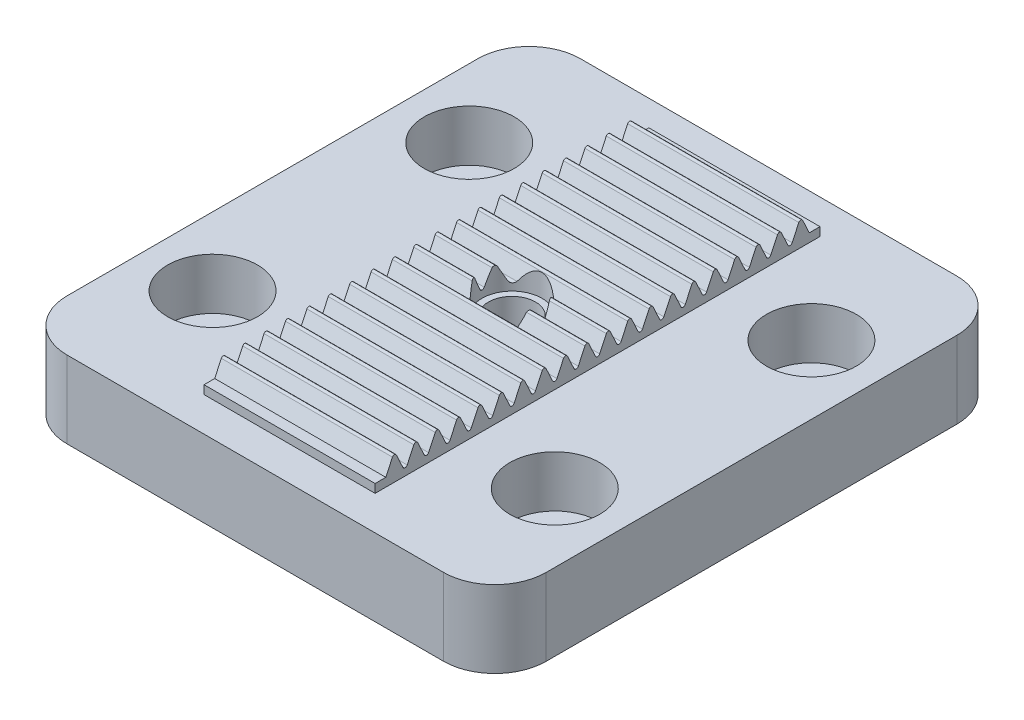
SolidWorks part; units mm, degrees
ref_plane "Front Plane" through (0, 0, 0) normal (0, 0, 1) x (1, 0, 0)
ref_plane "Top Plane" through (0, 0, 0) normal (0, 1, 0) x (1, 0, 0)
ref_plane "Right Plane" through (0, 0, 0) normal (1, 0, 0) x (0, 0, -1)
sketch "Sketch1" plane through (0, 0, 0) normal (0, 1, 0) x (1, 0, 0)
  line L1 (-28, -30) -> (28, -30)
  line L2 (-28, -30) -> (-28, 30)
  line L3 (-28, 30) -> (28, 30)
  line L4 (28, -30) -> (28, 30)
  line L5 (-28, -30) -> (28, 30) construction
  line L6 (-28, 30) -> (28, -30) construction
  line L7 (-20, -15) -> (20, -15) construction
  line L8 (-20, -15) -> (-20, 15) construction
  line L9 (-20, 15) -> (20, 15) construction
  line L10 (20, -15) -> (20, 15) construction
  line L11 (-20, -15) -> (20, 15) construction
  line L12 (-20, 15) -> (20, -15) construction
  circle A0 centre (-20, 15) radius 3.25
  circle A1 centre (-20, -15) radius 3.25
  circle A2 centre (20, -15) radius 3.25
  circle A3 centre (20, 15) radius 3 construction
  circle A4 centre (20, 15) radius 3.25
  point P0 (0, 0)
  point P6 (0, 0)
  point P17 (0, 0)
  point P18 (0, 0)
  dimension "D4" = 6
  dimension "D1" = 60
  dimension "D2" = 56
  dimension "D5" = 40
  dimension "D6" = 30
  dimension "D3" = 0.25
extrude "Boss-Extrude1" add sketch "Sketch1" along normal blind 3
sketch "Sketch2" plane through (0, 3, 0) normal (0, 1, 0) x (1, 0, 0)
  line L4 (28, -30) -> (28, 30)
  line L5 (28, 30) -> (-28, 30)
  line L6 (-28, 30) -> (-28, -30)
  line L7 (-28, -30) -> (28, -30)
  line L8 (28, -30) -> (28, 30)
  line L9 (28, 30) -> (-28, 30)
  line L10 (-28, 30) -> (-28, -30)
  line L11 (-28, -30) -> (28, -30)
  circle A0 centre (-20, 15) radius 5.25
  circle A1 centre (-20, -15) radius 5.25
  circle A2 centre (20, -15) radius 5.25
  circle A3 centre (20, 15) radius 5 construction
  circle A4 centre (20, 15) radius 5.25
  point P14 (0, 0)
  point P16 (18.0466, 14.3998)
  dimension "D3" = 10
  dimension "D2" = 0.25
extrude "Boss-Extrude2" add sketch "Sketch2" along normal blind 6
fillet "Fillet1" radius 6 4 edges at (28, 4.5, -30) (-28, 4.5, -30) (-28, 4.5, 30) (28, 4.5, 30)
sketch "Sketch3" plane through (0, 0, 0) normal (1, 0, 0) x (0, 0, -1)
  line L0 (-26, 9) -> (-26, 10)
  line L1 (-26, 10) -> (-24.75, 10)
  line L3 (24.75, 10) -> (26, 10)
  line L4 (26, 10) -> (26, 9)
  line L5 (26, 9) -> (-26, 9)
  line L6 (-26, 9) -> (-30, 9) construction
  line L7 (26, 9) -> (30, 9) construction
  line L8 (-24.75, 10) -> (-23.9766, 11.6586)
  line L9 (-23.5234, 11.6586) -> (-22.75, 10)
  line L10 (-23.75, 12.1445) -> (-23.75, 10) construction
  line L13 (-24.75, 10) -> (-22.75, 10) construction
  line L14 (-22.75, 10) -> (-22.25, 10) construction
  line L15 (-22.25, 10) -> (-21.4766, 11.6586)
  line L16 (-21.0234, 11.6586) -> (-20.25, 10)
  line L17 (-19.75, 10) -> (-18.9766, 11.6586)
  line L18 (-18.5234, 11.6586) -> (-17.75, 10)
  line L19 (-17.25, 10) -> (-16.4766, 11.6586)
  line L20 (-16.0234, 11.6586) -> (-15.25, 10)
  line L21 (-14.75, 10) -> (-13.9766, 11.6586)
  line L22 (-13.5234, 11.6586) -> (-12.75, 10)
  line L23 (-12.25, 10) -> (-11.4766, 11.6586)
  line L24 (-11.0234, 11.6586) -> (-10.25, 10)
  line L25 (-9.75, 10) -> (-8.9766, 11.6586)
  line L26 (-8.5234, 11.6586) -> (-7.75, 10)
  line L27 (-7.25, 10) -> (-6.4766, 11.6586)
  line L28 (-6.0234, 11.6586) -> (-5.25, 10)
  line L29 (-4.75, 10) -> (-3.9766, 11.6586)
  line L30 (-3.5234, 11.6586) -> (-2.75, 10)
  line L31 (-2.25, 10) -> (-1.4766, 11.6586)
  line L32 (-1.0234, 11.6586) -> (-0.25, 10)
  line L33 (0.25, 10) -> (1.0234, 11.6586)
  line L34 (1.4766, 11.6586) -> (2.25, 10)
  line L35 (2.75, 10) -> (3.5234, 11.6586)
  line L36 (3.9766, 11.6586) -> (4.75, 10)
  line L37 (5.25, 10) -> (6.0234, 11.6586)
  line L38 (6.4766, 11.6586) -> (7.25, 10)
  line L39 (7.75, 10) -> (8.5234, 11.6586)
  line L40 (8.9766, 11.6586) -> (9.75, 10)
  line L41 (10.25, 10) -> (11.0234, 11.6586)
  line L42 (11.4766, 11.6586) -> (12.25, 10)
  line L43 (12.75, 10) -> (13.5234, 11.6586)
  line L44 (13.9766, 11.6586) -> (14.75, 10)
  line L45 (15.25, 10) -> (16.0234, 11.6586)
  line L46 (16.4766, 11.6586) -> (17.25, 10)
  line L47 (17.75, 10) -> (18.5234, 11.6586)
  line L48 (18.9766, 11.6586) -> (19.75, 10)
  line L49 (20.25, 10) -> (21.0234, 11.6586)
  line L50 (21.4766, 11.6586) -> (22.25, 10)
  line L51 (22.75, 10) -> (23.5234, 11.6586)
  line L52 (23.9766, 11.6586) -> (24.75, 10)
  arc A0 (-23.9766, 11.6586) -> (-23.5234, 11.6586) centre (-23.75, 11.553) cw
  arc A1 (-22.75, 10) -> (-22.25, 10) centre (-22.5, 10.1166) ccw
  arc A2 (-21.4766, 11.6586) -> (-21.0234, 11.6586) centre (-21.25, 11.553) cw
  arc A3 (-20.25, 10) -> (-19.75, 10) centre (-20, 10.1166) ccw
  arc A4 (-18.9766, 11.6586) -> (-18.5234, 11.6586) centre (-18.75, 11.553) cw
  arc A5 (-17.75, 10) -> (-17.25, 10) centre (-17.5, 10.1166) ccw
  arc A6 (-16.4766, 11.6586) -> (-16.0234, 11.6586) centre (-16.25, 11.553) cw
  arc A7 (-15.25, 10) -> (-14.75, 10) centre (-15, 10.1166) ccw
  arc A8 (-13.9766, 11.6586) -> (-13.5234, 11.6586) centre (-13.75, 11.553) cw
  arc A9 (-12.75, 10) -> (-12.25, 10) centre (-12.5, 10.1166) ccw
  arc A10 (-11.4766, 11.6586) -> (-11.0234, 11.6586) centre (-11.25, 11.553) cw
  arc A11 (-10.25, 10) -> (-9.75, 10) centre (-10, 10.1166) ccw
  arc A12 (-8.9766, 11.6586) -> (-8.5234, 11.6586) centre (-8.75, 11.553) cw
  arc A13 (-7.75, 10) -> (-7.25, 10) centre (-7.5, 10.1166) ccw
  arc A14 (-6.4766, 11.6586) -> (-6.0234, 11.6586) centre (-6.25, 11.553) cw
  arc A15 (-5.25, 10) -> (-4.75, 10) centre (-5, 10.1166) ccw
  arc A16 (-3.9766, 11.6586) -> (-3.5234, 11.6586) centre (-3.75, 11.553) cw
  arc A17 (-2.75, 10) -> (-2.25, 10) centre (-2.5, 10.1166) ccw
  arc A18 (-1.4766, 11.6586) -> (-1.0234, 11.6586) centre (-1.25, 11.553) cw
  arc A19 (-0.25, 10) -> (0.25, 10) centre (0, 10.1166) ccw
  arc A20 (1.0234, 11.6586) -> (1.4766, 11.6586) centre (1.25, 11.553) cw
  arc A21 (2.25, 10) -> (2.75, 10) centre (2.5, 10.1166) ccw
  arc A22 (3.5234, 11.6586) -> (3.9766, 11.6586) centre (3.75, 11.553) cw
  arc A23 (4.75, 10) -> (5.25, 10) centre (5, 10.1166) ccw
  arc A24 (6.0234, 11.6586) -> (6.4766, 11.6586) centre (6.25, 11.553) cw
  arc A25 (7.25, 10) -> (7.75, 10) centre (7.5, 10.1166) ccw
  arc A26 (8.5234, 11.6586) -> (8.9766, 11.6586) centre (8.75, 11.553) cw
  arc A27 (9.75, 10) -> (10.25, 10) centre (10, 10.1166) ccw
  arc A28 (11.0234, 11.6586) -> (11.4766, 11.6586) centre (11.25, 11.553) cw
  arc A29 (12.25, 10) -> (12.75, 10) centre (12.5, 10.1166) ccw
  arc A30 (13.5234, 11.6586) -> (13.9766, 11.6586) centre (13.75, 11.553) cw
  arc A31 (14.75, 10) -> (15.25, 10) centre (15, 10.1166) ccw
  arc A32 (16.0234, 11.6586) -> (16.4766, 11.6586) centre (16.25, 11.553) cw
  arc A33 (17.25, 10) -> (17.75, 10) centre (17.5, 10.1166) ccw
  arc A34 (18.5234, 11.6586) -> (18.9766, 11.6586) centre (18.75, 11.553) cw
  arc A35 (19.75, 10) -> (20.25, 10) centre (20, 10.1166) ccw
  arc A36 (21.0234, 11.6586) -> (21.4766, 11.6586) centre (21.25, 11.553) cw
  arc A37 (22.25, 10) -> (22.75, 10) centre (22.5, 10.1166) ccw
  arc A38 (23.5234, 11.6586) -> (23.9766, 11.6586) centre (23.75, 11.553) cw
  arc A40 (24.75, 10) -> (25.25, 10) centre (25, 10.1166) ccw [skipped]
  point P15 (-23.75, 10)
  point P18 (-24.633, 8)
  point P20 (24.7824, 8)
  dimension "D4" = 0.25
  dimension "D1" = 4
  dimension "D2" = 50
  dimension "D3" = 2
  dimension "D5" = 1
  dimension "D7" = 0.5
  dimension "D8" = 20
extrude "Boss-Extrude3" add sketch "Sketch3" along normal mid plane 20
sketch "Sketch4" plane through (0, 0, 0) normal (0, 1, 0) x (1, 0, 0)
  line L0 (-28, 30) -> (28, -30) construction
  circle A0 centre (0, 0) radius 2.5 construction
  circle A1 centre (0, 0) radius 2.75
  dimension "D2" = 5
  dimension "D1" = 0.25
extrude "Cut-Extrude2" cut sketch "Sketch4" along normal through all
sketch "Sketch5" plane through (0, 9, 0) normal (0, 1, 0) x (1, 0, 0)
  circle A0 centre (0, 0) radius 3.5
  dimension "D1" = 7
extrude "Cut-Extrude3" cut sketch "Sketch5" along normal through all
sketch "Sketch6" plane through (0, 0, 0) normal (0, -1, 0) x (1, 0, 0)
  line L0 (-20, -15) -> (20, 15) construction
  line L1 (0, 4.6188) -> (-4, 2.3094) construction
  line L2 (-4, 2.3094) -> (-4, -2.3094) construction
  line L3 (-4, -2.3094) -> (0, -4.6188) construction
  line L4 (0, -4.6188) -> (4, -2.3094) construction
  line L5 (4, -2.3094) -> (4, 2.3094) construction
  line L6 (4, 2.3094) -> (0, 4.6188) construction
  line L7 (4.25, -2.4537) -> (4.25, 2.4537)
  line L8 (4.25, 2.4537) -> (0, 4.9075)
  line L9 (0, 4.9075) -> (-4.25, 2.4537)
  line L10 (-4.25, 2.4537) -> (-4.25, -2.4537)
  line L11 (-4.25, -2.4537) -> (0, -4.9075)
  line L12 (0, -4.9075) -> (4.25, -2.4537)
  circle A0 centre (0, 0) radius 4 construction
  point P16 (-0.2558, 4.6125)
  dimension "D1" = 0.25
  dimension "D2" = 8
extrude "Cut-Extrude4" cut sketch "Sketch6" against normal blind 5
equation "\"Tolerance\" = 0.25mm"
equation "\"Pocket_Head_M5\"= 8mm"
equation "\"Pocket_Head_M4\" = 7mm"
equation "\"Pocket_Nut_M4\" = 7mm"
equation "\"Pocket_Nut_M2.5\" = 5mm"
equation "\"Pocket_Nut_M5\"= 8mm"
equation "\"Pocket_Nut_M3\"= 5.5mm"
equation "\"Pocket_Head_M3\"= 5.5mm"
equation "\"Pocket_Head_M2.5\" = 4.7mm"
equation "\"D3@Sketch1\"=\"Tolerance\""
equation "\"D2@Sketch2\"=\"Tolerance\""
equation "\"Pocket_Head_M6\" = 10mm"
equation "\"D3@Sketch2\"=\"Pocket_Head_M6\""
equation "\"D1@Sketch4\"=\"Tolerance\""
equation "\"D1@Sketch6\"=\"Tolerance\""
equation "\"D2@Sketch6\"=\"Pocket_Nut_M5\""
